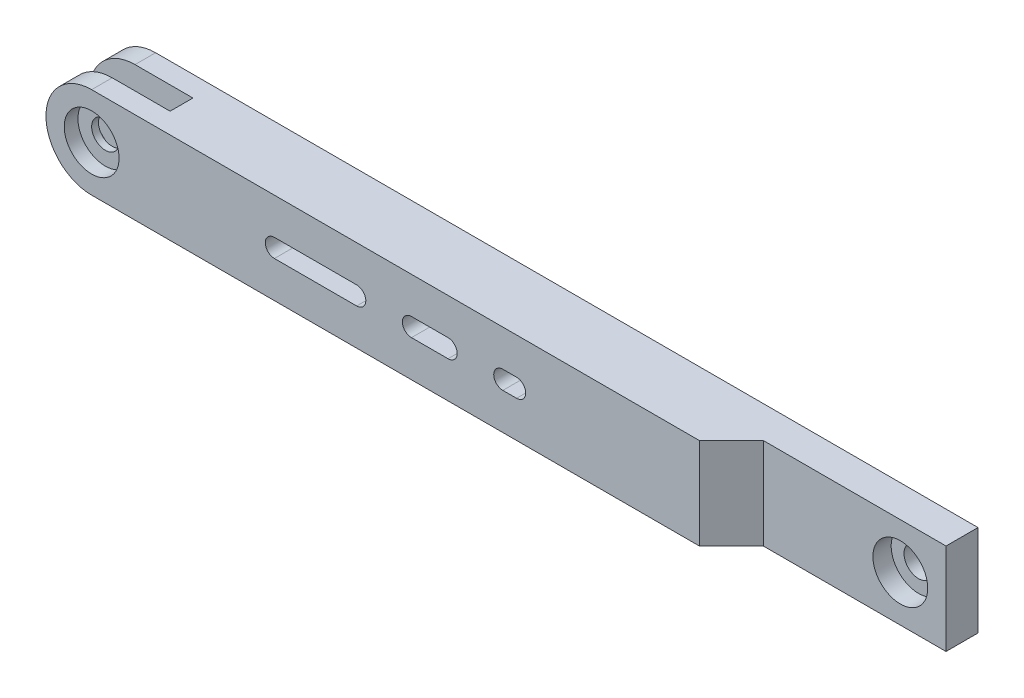
SolidWorks part; units mm, degrees
ref_plane "Front Plane" through (0, 0, 0) normal (0, 0, 1) x (1, 0, 0)
ref_plane "Top Plane" through (0, 0, 0) normal (0, 1, 0) x (1, 0, 0)
ref_plane "Right Plane" through (0, 0, 0) normal (1, 0, 0) x (0, 0, -1)
sketch "Sketch1" plane through (0, 0, 0) normal (0, 0, 1) x (1, 0, 0)
  line L0 (-50, -5) -> (28.0626, -5)
  line L2 (-50, -5) -> (-50, 5)
  line L5 (-50, -2.5) -> (50, 2.5) construction
  line L6 (-50, 2.5) -> (50, -2.5) construction
  line L7 (-50, 5) -> (28.0626, 5)
  line L8 (-50, -2.5) -> (-50, 2.5) construction
  line L9 (-52.5, -5) -> (27.6393, -5) construction
  line L10 (-52.5, 5) -> (27.6393, 5) construction
  line L11 (-52.5, -5) -> (-52.5, 5) construction
  line L12 (-50, -2.5) -> (27.6393, -2.5) construction
  line L13 (-50, 2.5) -> (27.6393, 2.5) construction
  circle A0 centre (50, 0) radius 17.5
  arc A1 (28.0626, -5) -> (28.0626, 5) centre (50, 0) ccw
  point P0 (0, 0)
  dimension "D3" = 35
  dimension "D4" = 45
  dimension "D1" = 5
  dimension "D2" = 100
  dimension "D6" = 100
  dimension "D7" = 2.5
extrude "Boss-Extrude1" add sketch "Sketch1" along normal blind 5
sketch "Sketch2" plane through (0, 0, 5) normal (0, 0, 1) x (1, 0, 0)
  circle A0 centre (50, 0) radius 22.5
  circle A1 centre (50, 0) radius 17.5 construction
  circle A2 centre (50, 0) radius 17.5
extrude "Boss-Extrude2" add sketch "Sketch2" along normal blind 11
chamfer "Chamfer1" distance 11 angle 65 1 edges
sketch "Sketch3" plane through (0, 0, 0) normal (0, 0, -1) x (-1, 0, 0)
  circle A0 centre (-50, 0) radius 17.5 construction
  arc A1 (-28.0626, 5) -> (-28.0626, -5) centre (-50, 0) ccw
  arc A2 (-28.0626, 5) -> (-28.0626, -5) centre (-50, 0) ccw
  circle A3 centre (-50, 0) radius 17.5
  arc A6 (-28.0626, -5) -> (-28.0626, 5) centre (-50, 0) ccw
  arc A7 (-28.0626, -5) -> (-28.0626, 5) centre (-50, 0) ccw
  dimension "D1" = 0
extrude "Cut-Extrude1" cut sketch "Sketch3" against normal blind 6
chamfer "Chamfer2" distance 11 angle 65 1 edges at (27.5, 0, 0)
sketch "Sketch4" plane through (0, -5, 0) normal (0, -1, 0) x (1, 0, 0)
  line L0 (33.8135, -10) -> (-83.4296, -10) construction
  line L1 (17.1559, 6) -> (-17.44, -10)
  line L2 (28.0626, 16) -> (-17.44, -5.0442)
  line L4 (-50, -10) -> (-17.44, -10)
  line L5 (-50, -10) -> (-50, -5.0442)
  line L6 (17.1559, 6) -> (28.0626, 6)
  line L7 (28.0626, 6) -> (28.0626, 16)
  line L8 (4.1824, 5) -> (-50, 5)
  line L9 (-50, 5) -> (-50, 0)
  line L10 (-50, 0) -> (4.1824, 0)
  line L11 (17.1559, 6) -> (28.0626, 6)
  line L12 (28.0626, 6) -> (28.0626, 16)
  line L16 (-50, -5.0442) -> (-17.44, -5.0442)
  spline S2 degree 3 poles (-951.0465, 295.8672) (60.8165, -720.9669) (-61.7624, 724.9848) (962.7555, -319.3221) knots -52.038528 -52.038528 -52.038528 -52.038528 51.564497 51.564497 51.564497 51.564497 only from (4.1824, 0) to (17.1559, 6)
  spline S3 degree 3 poles (838.4301, -569.9207) (324.1623, 145.2896) (168.7451, 80.9302) (-216.5346, -96.8043) (-440.8378, -222.2728) (-955.4617, 286.2069) knots -18.679639 -18.679639 -18.679639 -18.679639 0.5 0.5 29.734514 29.734514 29.734514 29.734514 only from (28.0626, 16) to (4.1824, 5)
  dimension "D2" = 24.82
  dimension "D1" = 0
sketch "Sketch6" plane through (0, 0, 0) normal (0, 0, -1) x (-1, 0, 0)
  line L3 (50, 5) -> (-4.1824, 5)
  line L4 (-4.1824, -5) -> (50, -5)
  line L5 (50, -5) -> (50, 5)
  line L6 (50, 5) -> (-28.0626, 5)
  line L7 (-28.0626, -5) -> (50, -5)
  line L8 (50, -5) -> (50, 5)
  arc A1 (-4.1824, -5) -> (-4.1824, 5) centre (-50, 0) ccw
  arc A2 (-28.0626, -5) -> (-28.0626, 5) centre (-50, 0) ccw construction
  arc A4 (-28.0626, -5) -> (-28.0626, 5) centre (-50, 0) ccw
  dimension "D1" = 0
extrude "Cut-Extrude2" cut sketch "Sketch6" against normal up to vertex
ref_plane "Plane1" through (0, 0, 0) normal (0, -1, 0) x (-1, 0, 0)
sketch "Sketch7" plane through (0, 0, 0) normal (0, -1, 0) x (-1, 0, 0)
  line L0 (-46.3566, -30.277) -> (-46.3566, 35.9379) construction
  line L1 (-95.8176, 10) -> (-150, 10) construction
  line L3 (-95.8176, 5) -> (-150, 5) construction
  line L4 (1.5538, 10) -> (-21.7637, -6)
  line L5 (3.1043, 5) -> (-27.5, -16)
  line L6 (-29.7966, -6) -> (-21.7637, -6)
  line L7 (3.1043, 5) -> (57.2867, 5)
  line L8 (57.2867, 5) -> (57.2867, 10)
  line L9 (1.5538, 10) -> (57.2867, 10)
  line L10 (-33.8135, 10) -> (83.4296, 10) construction
  line L11 (-17.1559, -6) -> (-28.0626, -6) construction
  line L12 (-29.7966, -6) -> (-29.7966, -16)
  line L13 (-72.5, -16) -> (-27.5, -16) construction
  line L14 (-29.7966, -16) -> (-27.5, -16)
  dimension "D1" = 34.457
  dimension "D2" = 5
extrude "Boss-Extrude3" add sketch "Sketch7" along normal mid plane 10
sketch "Sketch8" plane through (0, 0, -10) normal (0, 0, -1) x (-1, 0, 0)
  line L0 (5.7867, 1) -> (7.2867, 1)
  line L1 (17.2867, 5) -> (9.2867, 5) construction
  line L2 (17.2867, 5) -> (17.2867, 1) construction
  line L3 (17.2867, -5) -> (9.2867, -5) construction
  line L4 (9.2867, 5) -> (9.2867, -5) construction
  line L5 (17.2867, 5) -> (9.2867, -5) construction
  line L6 (17.2867, -5) -> (13.5563, -0.3369) construction
  line L7 (13.2867, 1) -> (17.2867, 1)
  line L8 (13.2867, 0) -> (9.2867, 5) construction
  line L9 (17.2867, -1) -> (13.2867, -1)
  line L10 (17.2867, -1) -> (17.2867, -5) construction
  line L11 (23.2867, 1) -> (32.2867, 1)
  line L12 (57.2867, -5) -> (57.2867, 5) construction
  line L13 (32.2867, -1) -> (23.2867, -1)
  line L14 (7.2867, -1) -> (5.7867, -1)
  arc A0 (13.2867, 1) -> (13.2867, -1) centre (13.2867, 0) ccw
  arc A1 (17.2867, -1) -> (17.2867, 1) centre (17.2867, 0) ccw
  arc A2 (23.2867, 1) -> (23.2867, -1) centre (23.2867, 0) ccw
  arc A3 (32.2867, -1) -> (32.2867, 1) centre (32.2867, 0) ccw
  arc A4 (7.2867, -1) -> (7.2867, 1) centre (7.2867, 0) ccw
  arc A5 (5.7867, 1) -> (5.7867, -1) centre (5.7867, 0) ccw
  point P0 (13.2867, 0)
  dimension "D4" = 2
  dimension "D5" = 2
  dimension "D1" = 6
  dimension "D2" = 6
  dimension "D3" = 10
  dimension "D6" = 4
  dimension "D7" = 9
  dimension "D8" = 1.5
  dimension "D9" = 25
extrude "Cut-Extrude3" cut sketch "Sketch8" against normal blind 10
sketch "Sketch9" plane through (0, 5, 0) normal (0, 1, 0) x (1, 0, 0)
  line L0 (-57.2867, 5) -> (-57.2867, 10) construction
  circle A0 centre (-47.2867, 7.5) radius 1
  dimension "D1" = 2
  dimension "D2" = 10
ref_plane "Plane2" through (0, 0, 0) normal (0, 1, 0) x (1, 0, 0)
sketch "Sketch10" plane through (0, 0, 0) normal (0, 1, 0) x (1, 0, 0)
  circle A0 centre (-47.2867, 7.5) radius 1 construction
  circle A1 centre (-47.2867, 7.5) radius 1
ref_plane "Plane3" through (0, 0, -7.5) normal (0, 0, -1) x (-1, 0, 0)
sketch "Sketch11" plane through (0, 0, -7.5) normal (0, 0, -1) x (-1, 0, 0)
  line L2 (51.2867, 4) -> (59.6147, 4)
  line L4 (59.6147, -4) -> (51.2867, -4)
  arc A0 (51.2867, 4) -> (51.2867, -4) centre (51.2867, 0) ccw
  dimension "D1" = 8
ref_plane "Plane4" through (-59.6147, 0, 0) normal (-1, 0, 0) x (0, 0, 1)
sketch "Sketch12" plane through (-59.6147, 0, 0) normal (-1, 0, 0) x (0, 0, 1)
  circle A0 centre (-7.5, 4) radius 0.875
  point P0 (-7.5, 4)
  dimension "D1" = 1.75
sweep "Cut-Sweep2" cut profiles "Sketch12" path "Sketch11"
sketch "Sketch13" plane through (0, 5, 0) normal (0, 1, 0) x (1, 0, 0)
  line L1 (-57.2867, 8.375) -> (-47.6529, 8.375)
  line L2 (-57.2867, 8.375) -> (-57.2867, 6.7053)
  line L3 (-57.2867, 6.7053) -> (-47.6529, 6.7053)
  line L4 (-47.6529, 8.375) -> (-47.6529, 6.7053)
  arc A0 (-47.2867, 6.625) -> (-47.2867, 8.375) centre (-47.2867, 7.5) ccw construction
  arc A1 (-47.2867, 8.375) -> (-47.2867, 6.625) centre (-47.2867, 7.5) ccw construction
extrude "Cut-Extrude4" cut sketch "Sketch13" against normal up to next
sketch "Sketch14" plane through (0, -5, 0) normal (0, -1, 0) x (1, 0, 0)
  line L0 (-47.6529, -6.7053) -> (-47.6529, -8.375) construction
  line L1 (-47.6529, -8.375) -> (-57.2867, -8.375) construction
  line L2 (-57.2867, -6.7053) -> (-47.6529, -6.7053) construction
  line L3 (-47.6529, -6.7053) -> (-47.6529, -8.375)
  line L4 (-47.6529, -8.375) -> (-57.2867, -8.375)
  line L5 (-57.2867, -6.7053) -> (-47.6529, -6.7053)
  line L6 (-57.2867, -8.375) -> (-57.2867, -6.7053)
extrude "Cut-Extrude5" cut sketch "Sketch14" against normal up to next
sketch "Sketch15" plane through (0, 0, 6) normal (0, 0, -1) x (-1, 0, 0)
  line L0 (-32.5, 0) -> (-21.7637, 0) construction
  line L1 (-21.7637, -5) -> (-21.7637, 5) construction
  line L2 (-21.7637, 0) -> (-21.7637, 5) construction
  line L3 (-34.6683, -0.5) -> (-21.2637, -0.5)
  line L4 (-21.2637, -0.5) -> (-21.2637, 5)
  line L5 (-34.6683, 0.5) -> (-22.2637, 0.5)
  line L6 (-22.2637, 0.5) -> (-22.2637, 5)
  line L7 (-34.6683, 0.5) -> (-34.6683, -0.5)
  line L8 (-21.2637, 5) -> (-22.2637, 5)
  line L9 (-32.5, 0.5) -> (-22.2637, 0.5) construction
  line L10 (-32.5, -0.5) -> (-21.2637, -0.5) construction
  circle A0 centre (-50, 0) radius 17.5 construction
  dimension "D1" = 0.5
  dimension "D2" = 0.5
extrude "Cut-Extrude6" cut sketch "Sketch15" against normal through all both and the other way through all
sketch "Sketch16" plane through (0, 5, 0) normal (0, 1, 0) x (1, 0, 0)
  line L0 (28.0626, -16) -> (28.0626, -6) construction
  circle A0 centre (28.0626, -11) radius 1.6
  dimension "D1" = 3.2
extrude "Cut-Extrude7" cut sketch "Sketch16" against normal through all both and the other way through all
sketch "Sketch17" plane through (0, 5, 0) normal (0, 1, 0) x (1, 0, 0)
  circle A0 centre (28.0626, -11) radius 3
  dimension "D1" = 6
extrude "Cut-Extrude8" cut sketch "Sketch17" along normal blind 10
sketch "Sketch18" plane through (0, -5, 0) normal (0, -1, 0) x (1, 0, 0)
  line L1 (28.0626, 7.8246) -> (30.8126, 9.4123)
  line L2 (30.8126, 9.4123) -> (30.8126, 12.5877)
  line L3 (30.8126, 12.5877) -> (28.0626, 14.1754)
  line L4 (28.0626, 14.1754) -> (25.3126, 12.5877)
  line L5 (25.3126, 12.5877) -> (25.3126, 9.4123)
  line L6 (25.3126, 9.4123) -> (28.0626, 7.8246)
  circle A0 centre (28.0626, 11) radius 2.75 construction
  dimension "D1" = 5.5
extrude "Cut-Extrude9" cut sketch "Sketch18" against normal blind 1 and the other way blind 10
sketch "Sketch20" plane through (0, -5, 0) normal (0, -1, 0) x (1, 0, 0)
  line L0 (-3.1043, -5) -> (10.5484, -5)
  line L1 (10.5484, -5) -> (10.5484, -10)
  line L2 (10.5484, -10) -> (-1.5538, -10)
sketch "Sketch21" plane through (0, -5, 0) normal (0, -1, 0) x (1, 0, 0)
  line L0 (-3.1043, -5) -> (10.5484, -5) construction
  line L1 (-3.1043, -5) -> (10.5484, -5)
  line L2 (-3.1043, -5) -> (-3.1043, 29.733)
  line L3 (-3.1043, 29.733) -> (79.6606, 29.733)
  line L4 (79.6606, 29.733) -> (79.6606, -13.4433)
  line L5 (79.6606, -13.4433) -> (18.5417, -5)
  line L6 (18.5417, -5) -> (-3.1043, -5)
  line M6 (-1.5538, -10) -> (21.7637, 6)
  line M7 (21.7637, 6) -> (28.0626, 6)
  line M8 (28.0626, 6) -> (28.0626, 7.8246)
  line M9 (28.0626, 7.8246) -> (25.3126, 9.4123)
  line M10 (25.3126, 9.4123) -> (25.3126, 12.5877)
  line M11 (25.3126, 12.5877) -> (28.0626, 14.1754)
  line M12 (28.0626, 14.1754) -> (28.0626, 16)
  line M13 (28.0626, 16) -> (27.5, 16)
  line M14 (27.5, 16) -> (-3.1043, -5)
extrude "Cut-Extrude11" cut sketch "Sketch21" against normal through all both and the other way through all contours L6 L5 L4 L3 L2 L1 M14 M13 M12 M11 M10 M9 M8 M7 M6 | L1 M14 M6 M7 M8 M9 M10 M11 M12 M13
sketch "Sketch22" plane through (0, -5, 0) normal (0, -1, 0) x (1, 0, 0)
  line L0 (-57.2867, -5) -> (-57.2867, 5.2015) construction
  line L1 (-57.2867, 5.2015) -> (17.7133, 5.2015) construction
  line L2 (5.7329, -5) -> (17.7133, -5)
  line L3 (17.7133, -5) -> (17.7133, -10)
  line L4 (17.7133, -10) -> (-1.5538, -10)
  line L5 (-1.5538, -10) -> (5.7329, -5)
  dimension "D1" = 75
extrude "Boss-Extrude4" add sketch "Sketch22" against normal up to vertex (10 mm away)
sketch "Sketch23" plane through (0, 0, -10) normal (0, 0, -1) x (-1, 0, 0)
  line L0 (-17.7133, 5) -> (-17.7133, -5) construction
  circle A0 centre (-12.7133, 0) radius 1.6
  dimension "D1" = 3.2
  dimension "D2" = 5
extrude "Cut-Extrude12" cut sketch "Sketch23" against normal through all
sketch "Sketch24" plane through (0, 0, -10) normal (0, 0, -1) x (-1, 0, 0)
  circle A0 centre (-12.7133, 0) radius 3
  dimension "D1" = 6
extrude "Cut-Extrude13" cut sketch "Sketch24" against normal blind 2
sketch "Sketch19" plane through (0, -5, 0) normal (0, -1, 0) x (1, 0, 0)
  line L0 (-47.6529, -8.375) -> (-47.6529, -6.7053) construction
  line L1 (-47.6529, -6.7053) -> (-45.0656, -6.7053)
  line L2 (-47.6529, -8.375) -> (-45.0656, -8.4553)
  arc A0 (-47.6529, -6.7053) -> (-47.6529, -8.375) centre (-47.6529, -7.5401) ccw
  arc A1 (-45.0656, -8.4553) -> (-45.0656, -6.7053) centre (-45.0656, -7.5803) ccw
  dimension "D1" = 1.75
extrude "Cut-Extrude10" cut sketch "Sketch19" against normal blind 10
sketch "Sketch25" plane through (-57.2867, 0, 0) normal (-1, 0, 0) x (0, 0, 1)
  line L0 (-5, -5) -> (-6.7053, -5) construction
  line L1 (-8.375, 5) -> (-6.625, 5)
  line L2 (-5, 5) -> (-6.7053, 5) construction
  line L3 (-8.375, 3) -> (-8.375, 5)
  line L4 (-6.625, -5) -> (-8.375, -5)
  line L5 (-6.625, 5) -> (-6.625, 3)
  line L6 (-6.625, -3) -> (-6.625, -5)
  line L8 (-8.375, -5) -> (-8.375, -3)
  arc A0 (-8.375, 3) -> (-6.625, 3) centre (-7.5, 3) ccw
  arc A1 (-6.625, -3) -> (-8.375, -3) centre (-7.5, -3) ccw
  dimension "D2" = 1.75
  dimension "D3" = 2
  dimension "D1" = 1.75
  dimension "D4" = 2
extrude "Cut-Extrude14" cut sketch "Sketch25" against normal up to vertex (12.2211 mm away)
sketch "Sketch27" plane through (0, -5, 0) normal (0, -1, 0) x (1, 0, 0)
  line L0 (-45.0656, -6.625) -> (-57.2867, -6.625) construction
  line L1 (-48.641, -8.375) -> (-45.0656, -8.375)
  line L2 (-48.641, -8.375) -> (-48.641, -6.625)
  line L3 (-48.641, -6.625) -> (-45.0656, -6.625)
  line L5 (-45.0656, -6.625) -> (-48.641, -6.625) construction
  arc A0 (-45.0656, -6.625) -> (-45.0656, -8.375) centre (-45.0656, -7.5) cw
sketch "Sketch28" plane through (0, 5, 0) normal (0, 1, 0) x (1, 0, 0)
  line L0 (-48.641, 6.625) -> (-45.0656, 6.625) construction
  line L2 (-47.8045, 6.625) -> (-45.0656, 6.625)
  line L4 (-47.6529, 8.375) -> (-45.0656, 8.4553) construction
  line L5 (-47.737, 8.3724) -> (-45.0656, 8.4553)
  arc A0 (-45.0656, 6.625) -> (-45.0656, 8.375) centre (-45.0656, 7.5) ccw construction
  arc A1 (-45.0656, 6.7053) -> (-45.0656, 8.4553) centre (-45.0656, 7.5803) ccw construction
  arc A2 (-45.0656, 6.625) -> (-44.1916, 7.5401) centre (-45.0656, 7.5) ccw
  arc A4 (-47.737, 8.3724) -> (-47.8045, 6.625) centre (-47.8045, 7.5) ccw
  arc A5 (-44.1916, 7.5401) -> (-45.0656, 8.4553) centre (-45.0656, 7.5803) ccw
extrude "Cut-Extrude15" cut sketch "Sketch28" against normal through all
sketch "Sketch29" plane through (0, 5, 0) normal (0, 1, 0) x (1, 0, 0)
  line L0 (-48.641, 8.375) -> (-45.0656, 8.375) construction
  line L1 (-47.6529, 8.375) -> (-45.0656, 8.4553) construction
  line L2 (-47.6529, 8.375) -> (-45.0656, 8.375)
  line L3 (-47.6529, 8.375) -> (-45.0656, 8.4553)
  arc A0 (-45.0656, 6.625) -> (-45.0656, 8.375) centre (-45.0656, 7.5) ccw construction
  arc A1 (-44.1916, 7.5401) -> (-45.0656, 8.4553) centre (-45.0656, 7.5803) ccw construction
  arc A2 (-44.1916, 7.5401) -> (-45.0656, 8.375) centre (-45.0656, 7.5) ccw
  arc A3 (-44.1916, 7.5401) -> (-45.0656, 8.4553) centre (-45.0656, 7.5803) ccw
extrude "Boss-Extrude5" add sketch "Sketch29" against normal up to vertex (10 mm away) up to point (-45.0656, -5, -6.625)
sketch "Sketch30" plane through (0, 0, -10) normal (0, 0, -1) x (-1, 0, 0)
  line L0 (57.2867, -5) -> (-17.7133, -5) construction
  line L1 (57.2867, 5) -> (38.4042, 5)
  line L2 (57.2867, 5) -> (57.2867, -5)
  line L3 (57.2867, -5) -> (38.4042, -5)
  line L4 (38.4042, 5) -> (38.4042, -5)
extrude "Boss-Extrude6" add sketch "Sketch30" against normal up to vertex (5 mm away)
sketch "Sketch31" plane through (0, 0, -5) normal (0, 0, 1) x (1, 0, 0)
  line L0 (-5.7867, -1) -> (-7.2867, -1) construction
  line L1 (-5.7867, -1) -> (-7.2867, -1)
  line L2 (-5.7867, 1) -> (-7.2867, 1)
  line L3 (-7.2867, -1) -> (-5.7867, -1)
  line L4 (17.7133, 5) -> (-57.2867, 5)
  line L5 (-57.2867, 5) -> (-57.2867, -5)
  line L6 (-57.2867, -5) -> (17.7133, -5)
  line L7 (17.7133, -5) -> (17.7133, 5)
  line L8 (17.7133, 5) -> (-57.2867, 5)
  line L9 (-57.2867, 5) -> (-57.2867, -5)
  line L10 (-57.2867, -5) -> (17.7133, -5)
  line L11 (17.7133, -5) -> (17.7133, 5)
  line L12 (-5.7867, 1) -> (-7.2867, 1)
  line L13 (-7.2867, -1) -> (-5.7867, -1)
  line L14 (-13.2867, 1) -> (-17.2867, 1)
  line L15 (-17.2867, -1) -> (-13.2867, -1)
  line L16 (-13.2867, 1) -> (-17.2867, 1)
  line L17 (-17.2867, -1) -> (-13.2867, -1)
  line L18 (-23.2867, 1) -> (-32.2867, 1)
  line L19 (-32.2867, -1) -> (-23.2867, -1)
  line L20 (-23.2867, 1) -> (-32.2867, 1)
  line L21 (-32.2867, -1) -> (-23.2867, -1)
  circle A1 centre (12.7133, 0) radius 1.6
  circle A2 centre (12.7133, 0) radius 1.6
  arc A4 (-5.7867, -1) -> (-5.7867, 1) centre (-5.7867, 0) ccw
  arc A5 (-7.2867, 1) -> (-7.2867, -1) centre (-7.2867, 0) ccw
  arc A6 (-5.7867, -1) -> (-5.7867, 1) centre (-5.7867, 0) ccw
  arc A7 (-7.2867, 1) -> (-7.2867, -1) centre (-7.2867, 0) ccw
  arc A8 (-13.2867, -1) -> (-13.2867, 1) centre (-13.2867, 0) ccw
  arc A9 (-17.2867, 1) -> (-17.2867, -1) centre (-17.2867, 0) ccw
  arc A10 (-13.2867, -1) -> (-13.2867, 1) centre (-13.2867, 0) ccw
  arc A11 (-17.2867, 1) -> (-17.2867, -1) centre (-17.2867, 0) ccw
  arc A12 (-23.2867, -1) -> (-23.2867, 1) centre (-23.2867, 0) ccw
  arc A13 (-32.2867, 1) -> (-32.2867, -1) centre (-32.2867, 0) ccw
  arc A14 (-23.2867, -1) -> (-23.2867, 1) centre (-23.2867, 0) ccw
  arc A15 (-32.2867, 1) -> (-32.2867, -1) centre (-32.2867, 0) ccw
  circle M18 centre (12.7133, 0) radius 1.6
  line M19 (-7.2867, 1) -> (-5.7867, 1)
  arc M20 (-5.7867, 1) -> (-5.7867, -1) centre (-5.7867, 0) cw
  line M21 (-5.7867, -1) -> (-7.2867, -1)
  arc M22 (-7.2867, -1) -> (-7.2867, 1) centre (-7.2867, 0) cw
  line M23 (-17.2867, 1) -> (-13.2867, 1)
  arc M24 (-13.2867, 1) -> (-13.2867, -1) centre (-13.2867, 0) cw
  line M25 (-13.2867, -1) -> (-17.2867, -1)
  arc M26 (-17.2867, -1) -> (-17.2867, 1) centre (-17.2867, 0) cw
  line M27 (-32.2867, 1) -> (-23.2867, 1)
  arc M28 (-23.2867, 1) -> (-23.2867, -1) centre (-23.2867, 0) cw
  line M29 (-23.2867, -1) -> (-32.2867, -1)
  arc M30 (-32.2867, -1) -> (-32.2867, 1) centre (-32.2867, 0) cw
  line M31 (17.7133, 5) -> (-57.2867, 5)
  line M32 (-57.2867, 5) -> (-57.2867, -5)
  line M33 (-57.2867, -5) -> (17.7133, -5)
  line M34 (17.7133, -5) -> (17.7133, 5)
  dimension "D1" = 0
  dimension "D2" = 0
  dimension "D3" = 0
  dimension "D4" = 0
  dimension "D5" = 0
extrude "Boss-Extrude7" add sketch "Sketch31" along normal blind 2 contours M34 M31 M32 M33 M22 M19 M20 M21 M30 M27 M28 M29 M26 M23 M24 M25 M18
sketch "Sketch32" plane through (0, 0, -10) normal (0, 0, -1) x (-1, 0, 0)
  line L0 (57.2867, -5) -> (57.2867, 5) construction
  circle A0 centre (42.2867, 0) radius 1.5
  dimension "D1" = 3
  dimension "D2" = 15
extrude "Cut-Extrude16" cut sketch "Sketch32" against normal through all
sketch "Sketch33" plane through (0, 5, 0) normal (0, 1, 0) x (1, 0, 0)
  line L0 (-45.7867, 6.5) -> (-45.7867, -5.7859) construction
  line L1 (-40.7867, 3) -> (-40.7867, 10) construction
  circle A0 centre (-48.2867, 6.5) radius 2.5
  dimension "D1" = 5
  dimension "D2" = 5
extrude "Cut-Extrude17" cut sketch "Sketch33" against normal blind 2 from offset 4 offset against normal yes
sketch "Sketch34" plane through (0, 5, 0) normal (0, 1, 0) x (1, 0, 0)
  line L0 (-43.7867, 10) -> (-43.7867, 3) construction
  line L1 (-47.9662, 7.25) -> (-39.6072, 7.25)
  line L2 (-47.9662, 7.25) -> (-47.9662, 5.75)
  line L3 (-47.9662, 5.75) -> (-39.6072, 5.75)
  line L4 (-39.6072, 7.25) -> (-39.6072, 5.75)
  line L5 (-47.9662, 7.25) -> (-39.6072, 5.75) construction
  line L6 (-47.9662, 5.75) -> (-39.6072, 7.25) construction
  point P0 (-43.7867, 6.5)
  dimension "D1" = 1.5
extrude "Cut-Extrude18" cut sketch "Sketch34" against normal through all
sketch "Sketch35" plane through (-57.2867, 0, 0) normal (-1, 0, 0) x (0, 0, 1)
  circle A0 centre (-6.5, 0) radius 2.125
  dimension "D1" = 4.25
extrude "Cut-Extrude19" cut sketch "Sketch35" against normal up to surface (17.6795 mm away) up to face at (-39.6072, 0, -6.5)
sketch "Sketch36" plane through (-57.2867, 0, 0) normal (-1, 0, 0) x (0, 0, 1)
  line L0 (-9, 1) -> (-9, -1) construction
  line L1 (-4, -1) -> (-4, 1) construction
  line L4 (-8.375, -1) -> (-9, -1) construction
  line L5 (-9, 1) -> (-8.375, 1) construction
  line L6 (-9, 1) -> (-9, -1)
  line L7 (-4, -1) -> (-4, 1)
  line L10 (-4, -1) -> (-9, -1)
  line L11 (-9, 1) -> (-4, 1)
extrude "Cut-Extrude20" cut sketch "Sketch36" against normal up to vertex (10.317 mm away)
sketch "Sketch37" plane through (-57.2867, 0, 0) normal (-1, 0, 0) x (0, 0, 1)
  line L1 (-7.25, -3.375) -> (-5.75, -3.375)
  line L2 (-7.25, -3.375) -> (-7.25, 3.375)
  line L3 (-7.25, 3.375) -> (-5.75, 3.375)
  line L4 (-5.75, -3.375) -> (-5.75, 3.375)
  line L5 (-7.25, -3.375) -> (-5.75, 3.375) construction
  line L6 (-7.25, 3.375) -> (-5.75, -3.375) construction
  point P0 (-6.5, 0)
  dimension "D1" = 6.75
  dimension "D2" = 1.5
extrude "Cut-Extrude21" cut sketch "Sketch37" against normal up to vertex (10.317 mm away)
sketch "Sketch38" plane through (-47.9662, 0, 0) normal (1, 0, 0) x (0, 0, -1)
  line L4 (5.75, 5) -> (5.75, 3.375)
  line L5 (5.75, 3.375) -> (7.25, 3.375)
  line L6 (7.25, 3.375) -> (7.25, 5)
  line L7 (7.25, 5) -> (5.75, 5)
  line L8 (5.75, 5) -> (5.75, 3.375)
  line L9 (5.75, 3.375) -> (7.25, 3.375)
  line L10 (7.25, 3.375) -> (7.25, 5)
  line L11 (7.25, 5) -> (5.75, 5)
  line L12 (7.25, -5) -> (7.25, -3.375)
  line L13 (7.25, -3.375) -> (5.75, -3.375)
  line L14 (5.75, -3.375) -> (5.75, -5)
  line L15 (5.75, -5) -> (7.25, -5)
  line L16 (7.25, -5) -> (7.25, -3.375)
  line L17 (7.25, -3.375) -> (5.75, -3.375)
  line L18 (5.75, -3.375) -> (5.75, -5)
  line L19 (5.75, -5) -> (7.25, -5)
  dimension "D1" = 0
  dimension "D2" = 0
extrude "Boss-Extrude8" add sketch "Sketch38" along normal up to vertex
sketch "Sketch39" plane through (0, 0, -3) normal (0, 0, 1) x (1, 0, 0)
  line L0 (-47.2867, 8.9827) -> (-47.2867, -11.1957) construction
  line L1 (-57.2867, 5) -> (-57.2867, -5) construction
  line L2 (17.7133, 5) -> (-57.2867, 5) construction
  line L3 (-57.2867, -5) -> (17.7133, -5) construction
  line L4 (-52.2922, 5) -> (-57.2867, 5)
  line L5 (-57.2867, 5) -> (-57.2867, -5)
  line L6 (-57.2867, -5) -> (-52.2922, -5)
  arc A0 (-52.2922, 5) -> (-52.2922, -5) centre (-52.2922, 0) ccw
  line M11 (17.7133, 5) -> (-57.2867, 5)
  line M12 (-57.2867, 5) -> (-57.2867, -5)
  line M13 (-57.2867, -5) -> (17.7133, -5)
  dimension "D1" = 10
extrude "Cut-Extrude22" cut sketch "Sketch39" against normal through all contours A0 M11 M12 | A0 M12 M13
sketch "Sketch40" plane through (0, 0, -3) normal (0, 0, 1) x (1, 0, 0)
  circle A0 centre (-42.2867, 0) radius 3
  dimension "D1" = 6
extrude "Cut-Extrude23" cut sketch "Sketch40" against normal blind 1
sketch "Sketch41" plane through (0, 0, -10) normal (0, 0, -1) x (-1, 0, 0)
  circle A0 centre (42.2867, 0) radius 1.5 construction
  circle A1 centre (42.2867, 0) radius 1.5
  circle A2 centre (42.2867, 0) radius 1.375
  dimension "D1" = 0.125
extrude "Boss-Extrude9" add sketch "Sketch41" against normal up to surface (1.375 mm away)
sketch "Sketch42" plane through (0, 0, -8) normal (0, 0, -1) x (-1, 0, 0)
  circle A0 centre (-12.7133, 0) radius 1.6 construction
  circle A1 centre (-12.7133, 0) radius 3
  circle A2 centre (-12.7133, 0) radius 3
  circle A3 centre (-12.7133, 0) radius 1.6
  dimension "D1" = 0
extrude "Boss-Extrude10" add sketch "Sketch42" along normal blind 2
sketch "Sketch43" plane through (0, 0, -3) normal (0, 0, 1) x (1, 0, 0)
  circle A0 centre (12.7133, 0) radius 3
  dimension "D1" = 6
extrude "Cut-Extrude24" cut sketch "Sketch43" against normal blind 2
ref_plane "Plane5" through (0, 0, -6.5) normal (0, 0, -1) x (-1, 0, 0)
sketch "Sketch44" plane through (0, 0, -6.5) normal (0, 0, -1) x (-1, 0, 0)
  line L0 (57.2867, 0) -> (66.5451, 0)
  line L1 (57.2867, 0.2329) -> (57.2867, -0.2329) construction
sketch "Sketch45" plane through (17.7133, 0, 0) normal (1, 0, 0) x (0, 0, -1)
  line L4 (3, -5) -> (10, -5)
  line L5 (10, -5) -> (10, 5)
  line L6 (10, 5) -> (3, 5)
  line L7 (3, 5) -> (3, -5)
  line L8 (3, -5) -> (10, -5)
  line L9 (10, -5) -> (10, 5)
  line L10 (10, 5) -> (3, 5)
  line L11 (3, 5) -> (3, -5)
  dimension "D1" = 0
extrude "Boss-Extrude11" add sketch "Sketch45" along normal blind 20
sketch "Sketch46" plane through (0, 0, -3) normal (0, 0, 1) x (1, 0, 0)
  line L0 (37.7133, 5) -> (37.7133, -5) construction
  circle A0 centre (32.7133, 0) radius 1.6
  dimension "D1" = 3.2
  dimension "D2" = 5
extrude "Cut-Extrude25" cut sketch "Sketch46" against normal through all
sketch "Sketch47" plane through (0, 0, -3) normal (0, 0, 1) x (1, 0, 0)
  circle A0 centre (32.7133, 0) radius 3
  dimension "D1" = 6
extrude "Cut-Extrude26" cut sketch "Sketch47" against normal up to surface (2 mm away) up to face at (15.7133, 0, -5)
sketch "Sketch48" plane through (0, 0, -3) normal (0, 0, 1) x (1, 0, 0)
  circle A0 centre (12.7133, 0) radius 3 construction
  circle A1 centre (12.7133, 0) radius 3
extrude "Boss-Extrude12" add sketch "Sketch48" against normal up to vertex (7 mm away)
sketch "Sketch49" plane through (0, -5, 0) normal (0, -1, 0) x (1, 0, 0)
  line L0 (37.7133, -6.5) -> (17.7133, -6.5)
  line L1 (37.7133, -3) -> (37.7133, -10) construction
  line L2 (17.7133, -6.5) -> (14.2133, -3)
  line L3 (-52.2922, -3) -> (37.7133, -3) construction
  line L4 (14.2133, -3) -> (37.7133, -3)
  line L5 (37.7133, -3) -> (37.7133, -6.5)
  dimension "D1" = 20
extrude "Cut-Extrude27" cut sketch "Sketch49" against normal up to vertex
sketch "Sketch50" plane through (0, 0, -6.5) normal (0, 0, 1) x (1, 0, 0)
  circle A0 centre (32.7133, 0) radius 3
  dimension "D1" = 6
extrude "Cut-Extrude28" cut sketch "Sketch50" against normal blind 2
sketch "Sketch51" plane through (0, 0, -3) normal (0, 0, 1) x (1, 0, 0)
  line L0 (-57.2867, 0.2329) -> (-57.2867, -0.2329) construction
  line L1 (-57.2867, 0.2329) -> (-57.2867, -0.2329)
  line L2 (-52.2922, 5) -> (-35.4549, 5)
  line L3 (14.2133, 5) -> (-52.2922, 5) construction
  line L4 (-35.4549, 5) -> (-35.4549, -5)
  line L5 (-52.2922, -5) -> (14.2133, -5) construction
  line L6 (-35.4549, -5) -> (-52.2922, -5)
  arc A0 (-52.2922, 5) -> (-57.2867, 0.2329) centre (-52.2922, 0) ccw construction
  arc A1 (-57.2867, -0.2329) -> (-52.2922, -5) centre (-52.2922, 0) ccw construction
  arc A2 (-52.2922, 5) -> (-57.2867, 0.2329) centre (-52.2922, 0) ccw
  arc A3 (-57.2867, -0.2329) -> (-52.2922, -5) centre (-52.2922, 0) ccw
extrude "Boss-Extrude13" add sketch "Sketch51" against normal up to vertex (7 mm away)
sketch "Sketch52" plane through (0, 0, -3) normal (0, 0, 1) x (1, 0, 0)
  circle A0 centre (-52.2922, 0) radius 1.5
  dimension "D1" = 3
extrude "Cut-Extrude29" cut sketch "Sketch52" against normal blind 10
sketch "Sketch53" plane through (0, 0, -3) normal (0, 0, 1) x (1, 0, 0)
  circle A0 centre (-52.2922, 0) radius 3
  dimension "D1" = 6
extrude "Cut-Extrude30" cut sketch "Sketch53" against normal blind 1.5
sketch "Sketch54" plane through (0, 5, 0) normal (0, 1, 0) x (1, 0, 0)
  line L0 (-57.2867, 6.5) -> (-66.5451, 6.5) construction
  line L1 (-87.1338, 5.25) -> (-45.9565, 5.25)
  line L2 (-87.1338, 5.25) -> (-87.1338, 7.75)
  line L3 (-87.1338, 7.75) -> (-45.9565, 7.75)
  line L4 (-45.9565, 5.25) -> (-45.9565, 7.75)
  line L5 (-87.1338, 5.25) -> (-45.9565, 7.75) construction
  line L6 (-87.1338, 7.75) -> (-45.9565, 5.25) construction
  point P0 (-66.5451, 6.5)
  dimension "D1" = 2.5
extrude "Cut-Extrude31" cut sketch "Sketch54" against normal through all
